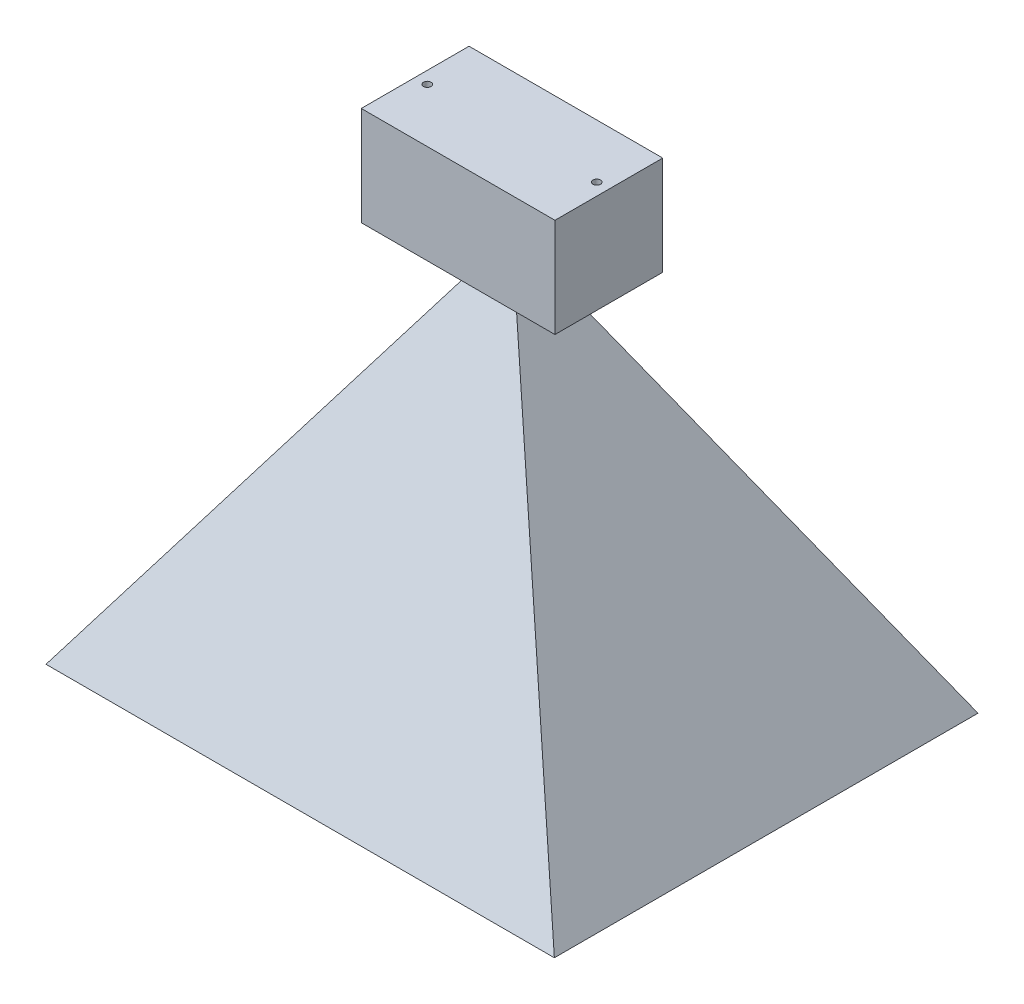
SolidWorks part; units mm, degrees
ref_plane "Front Plane" through (0, 0, 0) normal (0, 0, 1) x (1, 0, 0)
ref_plane "Top Plane" through (0, 0, 0) normal (0, 1, 0) x (1, 0, 0)
ref_plane "Right Plane" through (0, 0, 0) normal (1, 0, 0) x (0, 0, -1)
ref_plane "distance of measurement" through (0, 114.3, 0) normal (0, 1, 0) x (1, 0, 0)
sketch "Sketch1" plane through (0, 0, 0) normal (0, 1, 0) x (1, 0, 0)
  line L1 (-76.2, -63.5) -> (76.2, -63.5)
  line L2 (-76.2, -63.5) -> (-76.2, 63.5)
  line L3 (-76.2, 63.5) -> (76.2, 63.5)
  line L4 (76.2, -63.5) -> (76.2, 63.5)
  line L5 (-76.2, -63.5) -> (76.2, 63.5) construction
  line L6 (-76.2, 63.5) -> (76.2, -63.5) construction
  point P0 (0, 0)
  dimension "D1" = 152.4
  dimension "D2" = 127
sketch "Sketch2" plane through (0, 114.3, 0) normal (0, 1, 0) x (1, 0, 0)
  line L0 (-76.2, -63.5) -> (76.2, 63.5) construction
  line L1 (-2.4731, -2.0609) -> (2.4731, -2.0609)
  line L2 (-2.4731, -2.0609) -> (-2.4731, 2.0609)
  line L3 (-2.4731, 2.0609) -> (2.4731, 2.0609)
  line L4 (2.4731, -2.0609) -> (2.4731, 2.0609)
  line L5 (-2.4731, -2.0609) -> (2.4731, 2.0609) construction
  line L6 (-2.4731, 2.0609) -> (2.4731, -2.0609) construction
  point P0 (0, 0)
loft "FOV" add profiles "Sketch2", "Sketch1" connector at (-2.4731, 114.3, 2.0609) connector at (-76.2, 0, 63.5)
sketch "Sketch3" plane through (0, 114.3, 0) normal (0, 1, 0) x (1, 0, 0)
  circle A0 centre (0, 0) radius 8.509
  dimension "D1" = 17.018
extrude "camera lens" add sketch "Sketch3" along normal blind 0.254
sketch "Sketch4" plane through (0, 114.554, 0) normal (0, 1, 0) x (1, 0, 0)
  line L1 (29.0322, -16.1544) -> (-29.0322, -16.1544)
  line L2 (29.0322, -16.1544) -> (29.0322, 16.1544)
  line L3 (29.0322, 16.1544) -> (-29.0322, 16.1544)
  line L4 (-29.0322, -16.1544) -> (-29.0322, 16.1544)
  line L5 (29.0322, -16.1544) -> (-29.0322, 16.1544) construction
  line L6 (29.0322, 16.1544) -> (-29.0322, -16.1544) construction
  point P0 (0, 0)
  dimension "D1" = 58.0644
  dimension "D2" = 32.3088
extrude "camera holder" add sketch "Sketch4" along normal blind 29.6672
ref_point "centre of vision"
ref_point "direction reference"
sketch "reference points sketch" plane through (0, 0, 0) normal (0, -1, 0) x (1, 0, 0)
  line L0 (-76.2, 63.5) -> (76.2, 63.5) construction
  line L1 (76.2, 63.5) -> (76.2, -63.5) construction
  line L2 (76.2, -63.5) -> (-76.2, -63.5) construction
  line L3 (-76.2, -63.5) -> (-76.2, 63.5) construction
  line L4 (-76.2, 63.5) -> (76.2, -63.5) construction
  line L5 (-76.2, -63.5) -> (76.2, 63.5) construction
  point P0 (0, 63.5)
  point P1 (76.2, 0)
  point P4 (0, -63.5)
  point P7 (-76.2, 0)
  point P10 (-38.1, 0)
  point P13 (38.1, 0)
  point P14 (0, 31.75)
  point P15 (0, -31.75)
  point P16 (38.1, -31.75)
  point P17 (38.1, 31.75)
  point P20 (-38.1, 31.75)
  point P23 (-38.1, -31.75)
  point P24 (-76.2, 63.5)
  point P26 (76.2, 63.5)
  point P28 (76.2, -63.5)
  point P30 (-76.2, -63.5)
  dimension "D1" = 31.75
  dimension "D2" = 0
  dimension "D3" = 38.1
  dimension "D4" = 31.75
  dimension "D5" = 31.75
  dimension "D6" = 38.1
  dimension "D7" = 38.1
  dimension "D8" = 31.75
  dimension "D9" = 38.1
  dimension "D10" = 31.75
  dimension "D11" = 38.1
  dimension "D12" = 38.1
ref_point "direction reference 0"
ref_point "direction reference 1"
ref_point "direction reference 2"
ref_point "direction reference 3"
ref_point "direction reference 4"
ref_point "direction reference 5"
ref_point "direction reference 6"
ref_point "direction reference 7"
ref_point "direction reference 8"
ref_point "direction reference 9"
ref_point "direction reference 10"
ref_point "direction reference 11"
ref_point "direction reference 12"
ref_point "direction reference 13"
ref_point "direction reference 14"
ref_point "direction reference 15"
hole_wizard "#4-40 Tapped Hole1" positions "Sketch6" profile "Sketch5" tap size "#4-40" standard "ANSI Inch" end condition up to next
sketch "Sketch6" plane through (0, 144.2212, 0) normal (0, 1, 0) x (1, 0, 0)
  point P0 (-25.4, 0)
  point P2 (25.4, 0)
  dimension "D1" = 25.4
  dimension "D2" = 25.4
sketch "Sketch5" plane through (-25.4, 144.2212, 0) normal (1, 0, 0) x (0, 0, 1)
  line L0 (0, 0) -> (0, 29.6672)
  line L1 (0, 29.6672) -> (1.1303, 29.6672)
  line L2 (1.1303, 29.6672) -> (1.1303, 0)
  line L5 (1.1303, 0) -> (0, 0)
  line L11 (0, -6.35) -> (0, 107.95) construction
  dimension "Thru Tap Drill Dia." = 2.2606
  dimension "Thru Tap Drill Depth" = 29.6672
cosmetic thread "Hole Thread1" parameters "D2"=2.8448
cosmetic thread "Hole Thread2" parameters "D2"=2.8448
ref_point "z-basis"
ref_point "y-basis"
